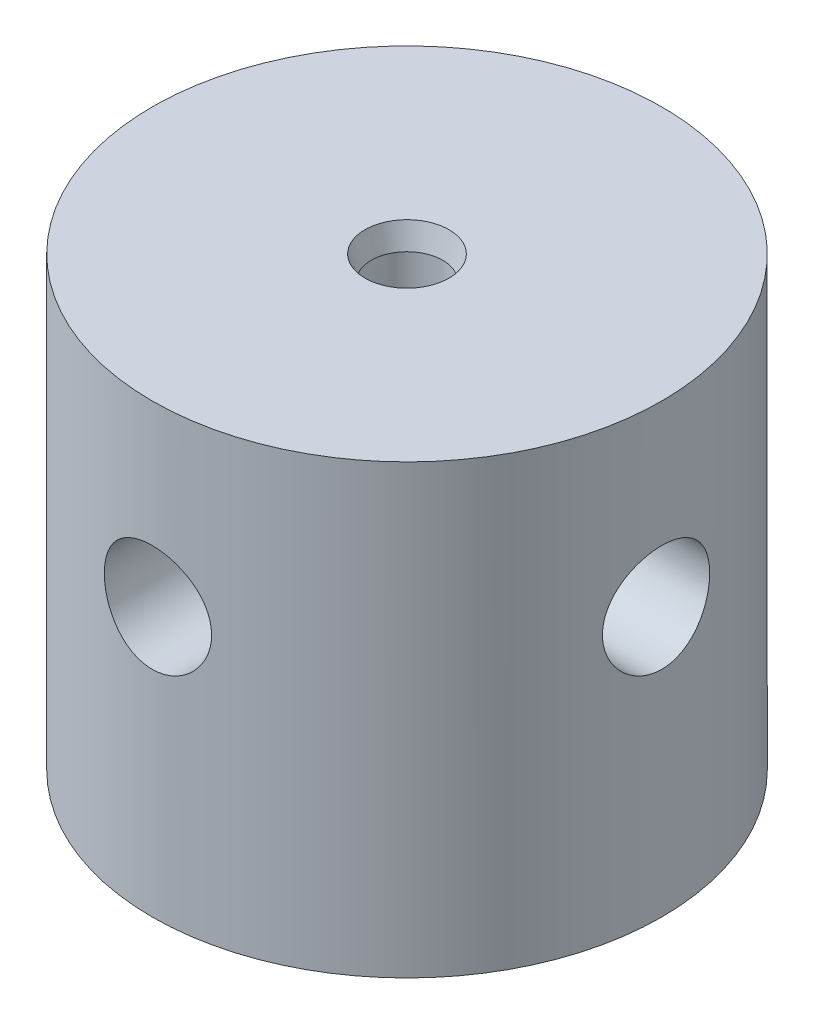
SolidWorks part; units mm, degrees
ref_plane "Front Plane" through (0, 0, 0) normal (0, 0, 1) x (1, 0, 0)
ref_plane "Top Plane" through (0, 0, 0) normal (0, 1, 0) x (1, 0, 0)
ref_plane "Right Plane" through (0, 0, 0) normal (1, 0, 0) x (0, 0, -1)
sketch "Sketch1" plane through (0, 0, 0) normal (0, 0, 1) x (1, 0, 0)
  line L0 (0, 20.7983) -> (0, -18.4168) construction
  line L1 (-12.7012, 0) -> (16.591, 0) construction
  line L2 (-2, 19.4024) -> (-2, -19.3364) construction
  line L3 (-2, 10.2057) -> (-2, -10.2057)
  line L4 (-2, -10.2057) -> (-14.25, -13.4881)
  line L5 (-14.25, 20.5926) -> (-14.25, -18.6225) construction
  line L6 (-2, 10.2057) -> (-2.35, 11.5119)
  line L7 (-2.35, 11.5119) -> (-14.25, 11.5119)
  line L8 (-14.25, 11.5119) -> (-14.25, -13.4881)
  point P10 (-2, 0)
  dimension "D1" = 25
  dimension "D2" = 14.25
  dimension "D3" = 15
  dimension "D4" = 2
  dimension "D5" = 2.35
  dimension "D6" = 75
revolve "Revolve1" add sketch "Sketch1" angle 360 about L0
ref_plane "Plane1" through (14.25, 0, 0) normal (1, 0, 0) x (0, 0, -1)
ref_axis "Axis1" through (0, -13.4881, 0) along (0, 1, 0)
sketch "Sketch2" plane through (14.25, 0, 0) normal (1, 0, 0) x (0, 0, -1)
  line L0 (0, -13.4881) -> (0, 11.5119) construction
  line L2 (2.35, 11.5119) -> (-2.35, 11.5119) construction
  circle A0 centre (0, 1.5119) radius 3
  dimension "D2" = 6
  dimension "D1" = 10
extrude "Cut-Extrude1" cut sketch "Sketch2" against normal blind 9
pattern_circular "CirPattern1" count 4 over 360 about axis through (0, -13.4881, 0) along (0, 1, 0) of "Cut-Extrude1"
